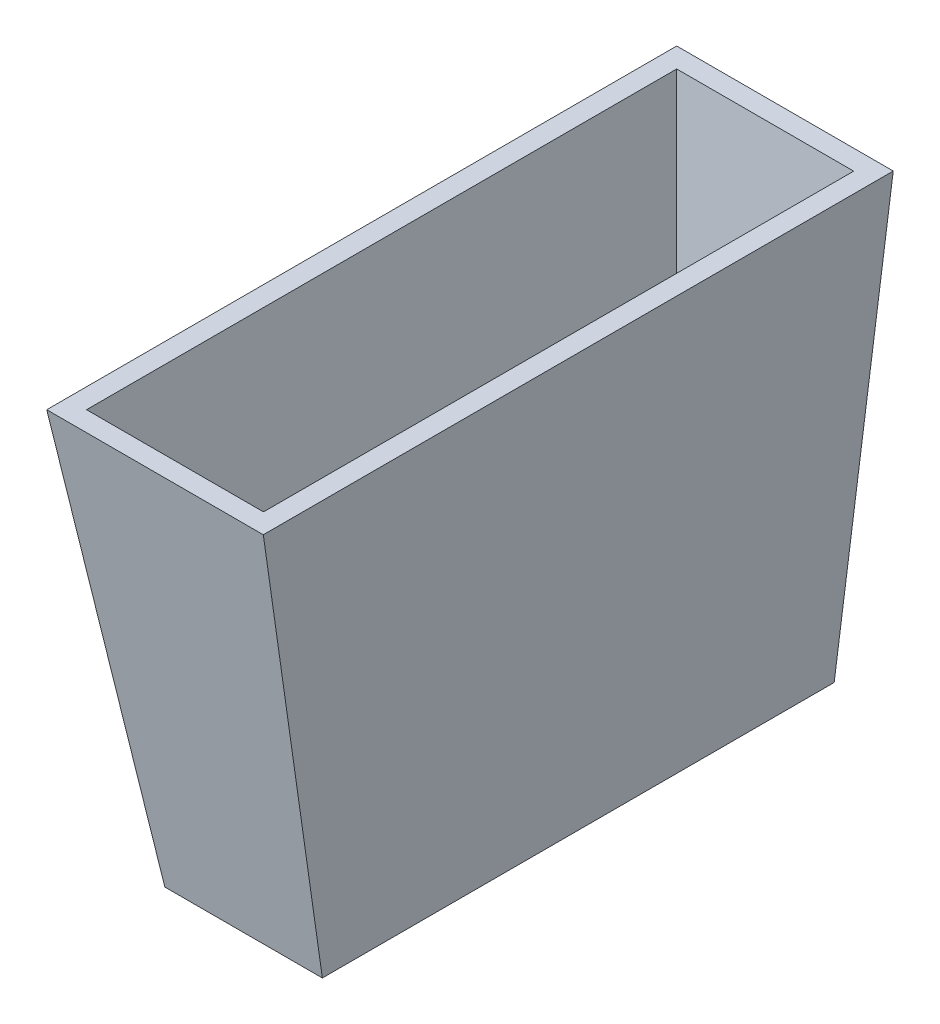
SolidWorks part; units mm, degrees
ref_plane "Front Plane" through (0, 0, 0) normal (0, 0, 1) x (1, 0, 0)
ref_plane "Top Plane" through (0, 0, 0) normal (0, 1, 0) x (1, 0, 0)
ref_plane "Right Plane" through (0, 0, 0) normal (1, 0, 0) x (0, 0, -1)
sketch "Sketch1" plane through (0, 0, 0) normal (0, 1, 0) x (1, 0, 0)
  line L0 (177.8, 330.2) -> (177.8, 0) construction
  line L1 (0, 0) -> (-101.6, 0)
  line L3 (0, 330.2) -> (-101.6, 330.2)
  line L4 (-101.6, 0) -> (-101.6, 330.2)
  line L15 (0, 330.2) -> (0, 0)
  dimension "D1" = 279.4
  dimension "D2" = 330.2
  dimension "D3" = 101.6
ref_plane "Plane1" through (0, 266.7, 0) normal (0, 1, 0) x (1, 0, 0)
sketch "Sketch2" plane through (0, 266.7, 0) normal (0, 1, 0) x (1, 0, 0)
  line L0 (-101.6, 165.1) -> (0, 165.1) construction
  line L1 (-139.7, -38.1) -> (0, -38.1)
  line L2 (-139.7, -38.1) -> (-139.7, 368.3)
  line L3 (-139.7, 368.3) -> (0, 368.3)
  line L13 (-101.6, 0) -> (-101.6, 330.2) construction
  line L16 (177.8, 330.2) -> (177.8, 0) construction
  line L21 (0, 368.3) -> (0, -38.1)
  point P14 (-139.7, 165.1)
  dimension "D1" = 406.4
  dimension "D2" = 317.5
  dimension "D3" = 139.7
loft "Loft4" add profiles "Sketch1", "Sketch2" connector at (0, 0, 0) connector at (0, 266.7, 38.1)
shell "Shell1" thickness 12.7 removed face at (-69.85, 266.7, -165.1)
